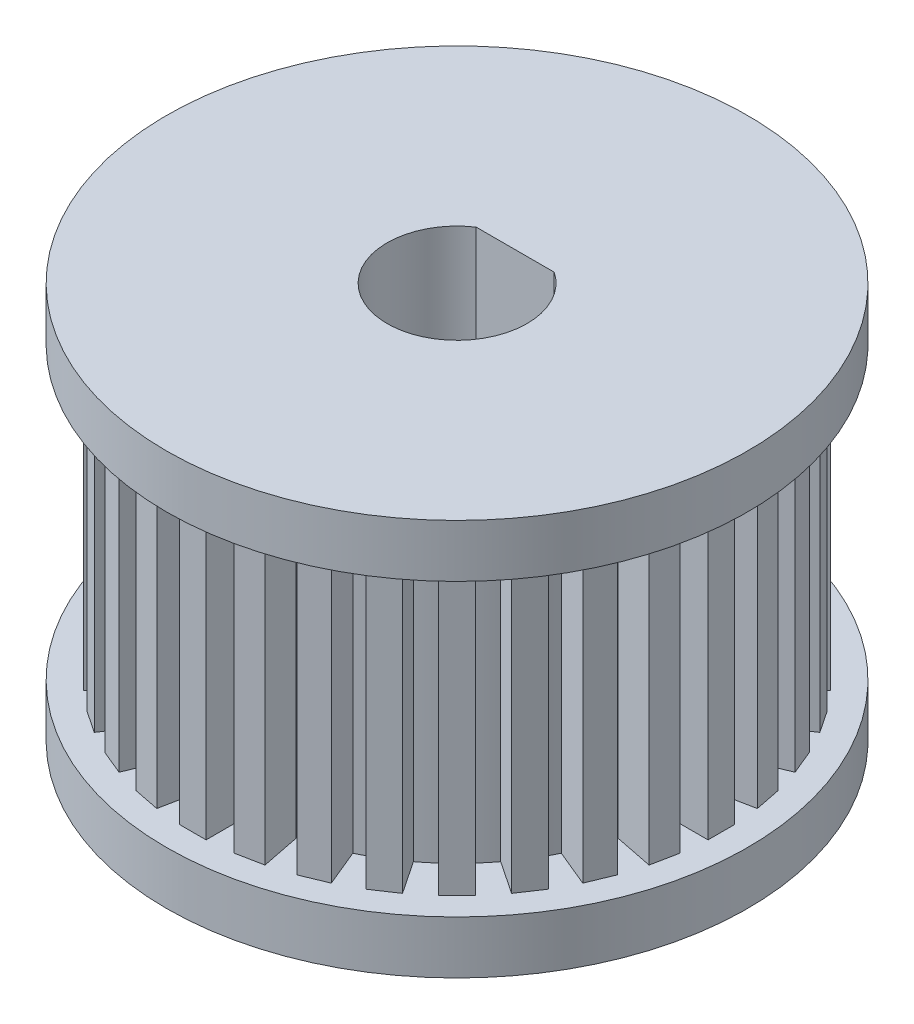
SolidWorks part; units mm, degrees
ref_plane "Front Plane" through (0, 0, 0) normal (0, 0, 1) x (1, 0, 0)
ref_plane "Top Plane" through (0, 0, 0) normal (0, 1, 0) x (1, 0, 0)
ref_plane "Right Plane" through (0, 0, 0) normal (1, 0, 0) x (0, 0, -1)
sketch "Sketch1" plane through (0, 0, 0) normal (0, 1, 0) x (1, 0, 0)
  line L0 (0, 14.8158) -> (0, -14.5532) construction
  line L1 (-0.5, 10) -> (0.5, 10)
  line L2 (0.5, 10) -> (0.5, 8.5)
  line L3 (-0.5, 10) -> (-0.5, 8.5)
  line L4 (-1.4773, 2.2) -> (1.4773, 2.2)
  line L5 (1.4605, 9.9054) -> (1.1679, 8.4342)
  line L6 (1.4605, 9.9054) -> (2.4413, 9.7103)
  line L7 (2.4413, 9.7103) -> (2.1487, 8.2391)
  line L8 (3.3649, 9.4301) -> (2.7909, 8.0443)
  line L9 (3.3649, 9.4301) -> (4.2888, 9.0475)
  line L10 (4.2888, 9.0475) -> (3.7147, 7.6616)
  line L11 (5.14, 8.5925) -> (4.3066, 7.3453)
  line L12 (5.14, 8.5925) -> (5.9714, 8.0369)
  line L13 (5.9714, 8.0369) -> (5.1381, 6.7897)
  line L14 (6.7175, 7.4246) -> (5.6569, 6.364)
  line L15 (6.7175, 7.4246) -> (7.4246, 6.7175)
  line L16 (7.4246, 6.7175) -> (6.364, 5.6569)
  line L17 (8.0369, 5.9714) -> (6.7897, 5.1381)
  line L18 (8.0369, 5.9714) -> (8.5925, 5.14)
  line L19 (8.5925, 5.14) -> (7.3453, 4.3066)
  line L20 (9.0475, 4.2888) -> (7.6616, 3.7147)
  line L21 (9.0475, 4.2888) -> (9.4301, 3.3649)
  line L22 (9.4301, 3.3649) -> (8.0443, 2.7909)
  line L23 (9.7103, 2.4413) -> (8.2391, 2.1487)
  line L24 (9.7103, 2.4413) -> (9.9054, 1.4605)
  line L25 (9.9054, 1.4605) -> (8.4342, 1.1679)
  line L26 (10, 0.5) -> (8.5, 0.5)
  line L27 (10, 0.5) -> (10, -0.5)
  line L28 (10, -0.5) -> (8.5, -0.5)
  line L29 (9.9054, -1.4605) -> (8.4342, -1.1679)
  line L30 (9.9054, -1.4605) -> (9.7103, -2.4413)
  line L31 (9.7103, -2.4413) -> (8.2391, -2.1487)
  line L32 (9.4301, -3.3649) -> (8.0443, -2.7909)
  line L33 (9.4301, -3.3649) -> (9.0475, -4.2888)
  line L34 (9.0475, -4.2888) -> (7.6616, -3.7147)
  line L35 (8.5925, -5.14) -> (7.3453, -4.3066)
  line L36 (8.5925, -5.14) -> (8.0369, -5.9714)
  line L37 (8.0369, -5.9714) -> (6.7897, -5.1381)
  line L38 (7.4246, -6.7175) -> (6.364, -5.6569)
  line L39 (7.4246, -6.7175) -> (6.7175, -7.4246)
  line L40 (6.7175, -7.4246) -> (5.6569, -6.364)
  line L41 (5.9714, -8.0369) -> (5.1381, -6.7897)
  line L42 (5.9714, -8.0369) -> (5.14, -8.5925)
  line L43 (5.14, -8.5925) -> (4.3066, -7.3453)
  line L44 (4.2888, -9.0475) -> (3.7147, -7.6616)
  line L45 (4.2888, -9.0475) -> (3.3649, -9.4301)
  line L46 (3.3649, -9.4301) -> (2.7909, -8.0443)
  line L47 (2.4413, -9.7103) -> (2.1487, -8.2391)
  line L48 (2.4413, -9.7103) -> (1.4605, -9.9054)
  line L49 (1.4605, -9.9054) -> (1.1679, -8.4342)
  line L50 (0.5, -10) -> (0.5, -8.5)
  line L51 (0.5, -10) -> (-0.5, -10)
  line L52 (-0.5, -10) -> (-0.5, -8.5)
  line L53 (-1.4605, -9.9054) -> (-1.1679, -8.4342)
  line L54 (-1.4605, -9.9054) -> (-2.4413, -9.7103)
  line L55 (-2.4413, -9.7103) -> (-2.1487, -8.2391)
  line L56 (-3.3649, -9.4301) -> (-2.7909, -8.0443)
  line L57 (-3.3649, -9.4301) -> (-4.2888, -9.0475)
  line L58 (-4.2888, -9.0475) -> (-3.7147, -7.6616)
  line L59 (-5.14, -8.5925) -> (-4.3066, -7.3453)
  line L60 (-5.14, -8.5925) -> (-5.9714, -8.0369)
  line L61 (-5.9714, -8.0369) -> (-5.1381, -6.7897)
  line L62 (-6.7175, -7.4246) -> (-5.6569, -6.364)
  line L63 (-6.7175, -7.4246) -> (-7.4246, -6.7175)
  line L64 (-7.4246, -6.7175) -> (-6.364, -5.6569)
  line L65 (-8.0369, -5.9714) -> (-6.7897, -5.1381)
  line L66 (-8.0369, -5.9714) -> (-8.5925, -5.14)
  line L67 (-8.5925, -5.14) -> (-7.3453, -4.3066)
  line L68 (-9.0475, -4.2888) -> (-7.6616, -3.7147)
  line L69 (-9.0475, -4.2888) -> (-9.4301, -3.3649)
  line L70 (-9.4301, -3.3649) -> (-8.0443, -2.7909)
  line L71 (-9.7103, -2.4413) -> (-8.2391, -2.1487)
  line L72 (-9.7103, -2.4413) -> (-9.9054, -1.4605)
  line L73 (-9.9054, -1.4605) -> (-8.4342, -1.1679)
  line L74 (-10, -0.5) -> (-8.5, -0.5)
  line L75 (-10, -0.5) -> (-10, 0.5)
  line L76 (-10, 0.5) -> (-8.5, 0.5)
  line L77 (-9.9054, 1.4605) -> (-8.4342, 1.1679)
  line L78 (-9.9054, 1.4605) -> (-9.7103, 2.4413)
  line L79 (-9.7103, 2.4413) -> (-8.2391, 2.1487)
  line L80 (-9.4301, 3.3649) -> (-8.0443, 2.7909)
  line L81 (-9.4301, 3.3649) -> (-9.0475, 4.2888)
  line L82 (-9.0475, 4.2888) -> (-7.6616, 3.7147)
  line L83 (-8.5925, 5.14) -> (-7.3453, 4.3066)
  line L84 (-8.5925, 5.14) -> (-8.0369, 5.9714)
  line L85 (-8.0369, 5.9714) -> (-6.7897, 5.1381)
  line L86 (-7.4246, 6.7175) -> (-6.364, 5.6569)
  line L87 (-7.4246, 6.7175) -> (-6.7175, 7.4246)
  line L88 (-6.7175, 7.4246) -> (-5.6569, 6.364)
  line L89 (-5.9714, 8.0369) -> (-5.1381, 6.7897)
  line L90 (-5.9714, 8.0369) -> (-5.14, 8.5925)
  line L91 (-5.14, 8.5925) -> (-4.3066, 7.3453)
  line L92 (-4.2888, 9.0475) -> (-3.7147, 7.6616)
  line L93 (-4.2888, 9.0475) -> (-3.3649, 9.4301)
  line L94 (-3.3649, 9.4301) -> (-2.7909, 8.0443)
  line L95 (-2.4413, 9.7103) -> (-2.1487, 8.2391)
  line L96 (-2.4413, 9.7103) -> (-1.4605, 9.9054)
  line L97 (-1.4605, 9.9054) -> (-1.1679, 8.4342)
  circle A0 centre (0, 0) radius 11
  circle A1 centre (0, 0) radius 8.5147
  arc A2 (-1.4773, 2.2) -> (1.4773, 2.2) centre (0, 0) ccw
  point P12 (0, 0)
  point P13 (-5.9714, 8.0443)
  point P139 (0, 0)
  dimension "D1" = 22
  dimension "D5" = 2.65
  dimension "D2" = 1
  dimension "D3" = 1.5
  dimension "D4" = 10
  dimension "D6" = 2.2
  dimension "D7" = 32
extrude "Boss-Extrude1" add sketch "Sketch1" along normal blind 15 contours A1 L97 L96 L95 | A1 L94 L93 L92 | A1 L91 L90 L89 | A1 L88 L87 L86 | A1 L85 L84 L83 | A1 L82 L81 L80 | A1 L79 L78 L77 | A1 L76 L75 L74 | A1 L73 L72 L71 | A1 L70 L69 L68 | A1 L67 L66 L65 | A1 L64 L63 L62 | A1 L61 L60 L59 | A1 L58 L57 L56 | A1 L55 L54 L53 | A1 L7 L6 L5 | A1 L10 L9 L8 | A1 L13 L12 L11 | A1 L16 L15 L14 | A1 L19 L18 L17 | A1 L22 L21 L20 | A1 L25 L24 L23 | A1 L28 L27 L26 | A1 L31 L30 L29 | A1 L34 L33 L32 | A1 L37 L36 L35 | A1 L40 L39 L38 | A1 L43 L42 L41 | A1 L46 L45 L44 | A1 L49 L48 L47 | L0 A1 L52 L51 | A1 L0 L51 L50 | L0 L1 L3 A1 | L1 L0 A1 L2 | L0 A1 A2 L4 | A1 L0 L4 A2 region at (0.2504, 0, -9.2549) region at (-0.2504, 0, -9.2549) region at (3.8662, 0, -0.0104) region at (-3.8662, 0, -0.0104) region at (-0.2504, 0, 9.2549) region at (0.2504, 0, 9.2549) region at (1.8055, 0, -9.0771) region at (-1.8055, 0, -9.0771) region at (-1.8055, 0, 9.0771) region at (1.8055, 0, 9.0771) region at (3.5417, 0, -8.5504) region at (-3.5417, 0, -8.5504) region at (-3.5417, 0, 8.5504) region at (3.5417, 0, 8.5504) region at (5.1417, 0, -7.6952) region at (-5.1417, 0, -7.6952) region at (-5.1417, 0, 7.6952) region at (5.1417, 0, 7.6952) region at (6.5442, 0, -6.5442) region at (-6.5442, 0, -6.5442) region at (-6.5442, 0, 6.5442) region at (6.5442, 0, 6.5442) region at (7.6952, 0, -5.1417) region at (-7.6952, 0, -5.1417) region at (-7.6952, 0, 5.1417) region at (7.6952, 0, 5.1417) region at (8.5504, 0, -3.5417) region at (-8.5504, 0, -3.5417) region at (-8.5504, 0, 3.5417) region at (8.5504, 0, 3.5417) region at (9.0771, 0, -1.8055) region at (-9.0771, 0, -1.8055) region at (-9.0771, 0, 1.8055) region at (9.0771, 0, 1.8055) region at (9.2549, 0, 0) region at (-9.2549, 0, 0)
extrude "Boss-Extrude2" add sketch "Sketch1<4>" along normal blind 2 contours L0 A0 L51 L52 A1 L53 L54 L55 L56 L57 L58 L59 L60 L61 L62 L63 L64 L65 L66 L67 L68 L69 L70 L71 L72 L73 L74 L75 L76 L77 L78 L79 L80 L81 L82 L83 L84 L85 L86 | A0 L0 L1 L2 A1 L5 L6 L7 L8 L9 L10 L11 L12 L13 L14 L15 L16 L17 L18 L19 L20 L21 L22 L23 L24 L25 L26 L27 L28 L29 L30 L31 L32 L33 L34 L35 L36 L37 L38 L39 region at (7.6042, 0, -7.6042) region at (-0.246, 0, -10.5)
sketch "Sketch1<4>" plane through (0, 0, 0) normal (0, 1, 0) x (1, 0, 0) same geometry as "Sketch1"
extrude "Boss-Extrude3" add sketch "Sketch1<5>" against normal blind 2 from surface contours L0 A0 L51 L52 A1 L53 L54 L55 L56 L57 L58 L59 L60 L61 L62 L63 L64 L65 L66 L67 L68 L69 L70 L71 L72 L73 L74 L75 L76 L77 L78 L79 L80 L81 L82 L83 L84 L85 L86 | A0 L0 L1 L2 A1 L5 L6 L7 L8 L9 L10 L11 L12 L13 L14 L15 L16 L17 L18 L19 L20 L21 L22 L23 L24 L25 L26 L27 L28 L29 L30 L31 L32 L33 L34 L35 L36 L37 L38 L39 region at (7.6042, 0, -7.6042) region at (-0.246, 0, -10.5) starting at face at (0, 15, 0)
sketch "Sketch1<5>" plane through (0, 0, 0) normal (0, 1, 0) x (1, 0, 0) same geometry as "Sketch1"
